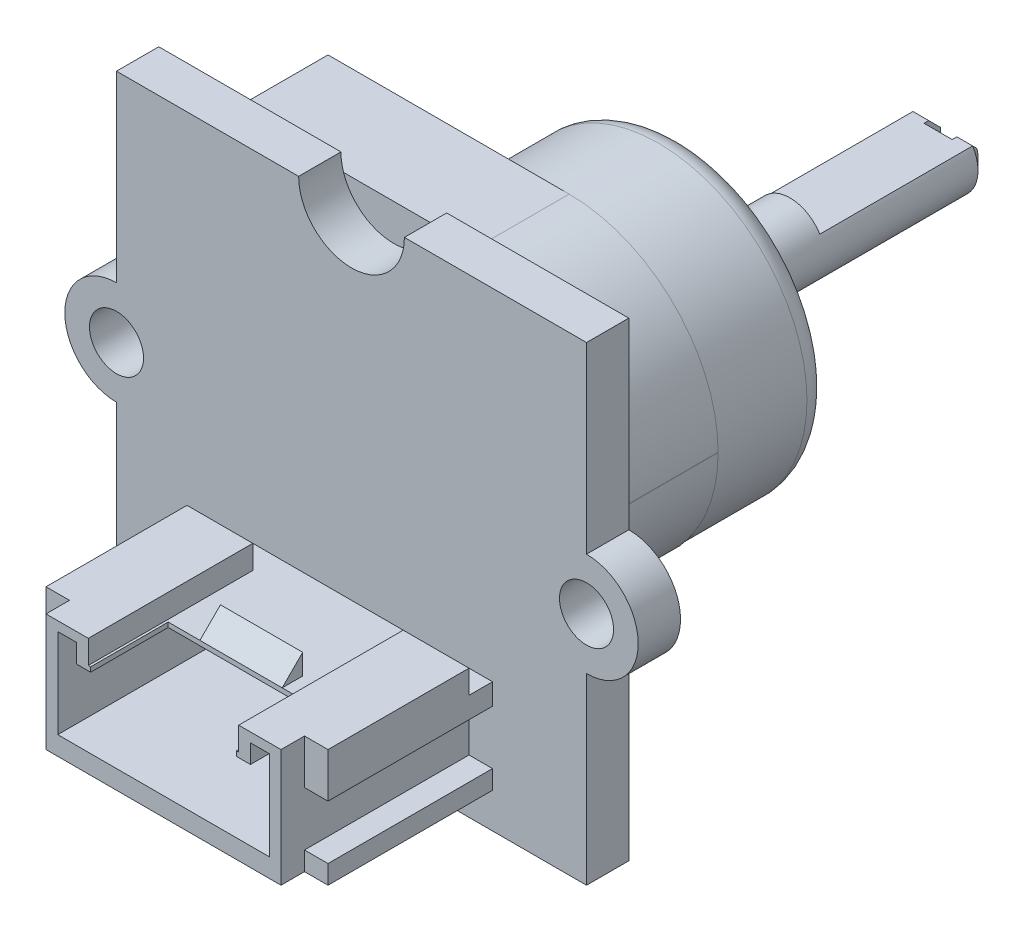
SolidWorks part; units mm, degrees
ref_plane "Plan de face" through (0, 0, 0) normal (0, 0, 1) x (1, 0, 0)
ref_plane "Plan de dessus" through (0, 0, 0) normal (0, 1, 0) x (1, 0, 0)
ref_plane "Plan de droite" through (0, 0, 0) normal (1, 0, 0) x (0, 0, -1)
sketch "Esquisse1" plane through (0, 0, 0) normal (0, 0, 1) x (1, 0, 0)
  line L0 (-2.7446, 10.9929) -> (-2.7446, -9.0071) construction
  line L1 (-12.7446, 10.9929) -> (-4.9946, 10.9929)
  line L2 (-12.7446, 10.9929) -> (-12.7446, 3.1929)
  line L3 (-12.7446, -9.0071) -> (-4.9946, -9.0071)
  line L4 (7.2554, 10.9929) -> (7.2554, 3.1929)
  line L5 (-12.7446, 0.9929) -> (7.2554, 0.9929) construction
  line L6 (-0.4946, 10.9929) -> (7.2554, 10.9929)
  line L7 (-0.4946, -9.0071) -> (7.2554, -9.0071)
  line L8 (-12.7446, -1.2071) -> (-12.7446, -9.0071)
  line L9 (7.2554, -1.2071) -> (7.2554, -9.0071)
  arc A0 (-4.9946, 10.9929) -> (-0.4946, 10.9929) centre (-2.7446, 10.9929) ccw
  arc A1 (-0.4946, -9.0071) -> (-4.9946, -9.0071) centre (-2.7446, -9.0071) ccw
  arc A2 (-12.7446, 3.1929) -> (-12.7446, -1.2071) centre (-12.7446, 0.9929) ccw
  arc A3 (7.2554, -1.2071) -> (7.2554, 3.1929) centre (7.2554, 0.9929) ccw
  circle A4 centre (-12.7446, 0.9929) radius 1.15
  circle A5 centre (7.2554, 0.9929) radius 1.15
  dimension "D1" = 20
  dimension "D2" = 20
extrude "Boss.-Extru.1" add sketch "Esquisse1" along normal blind 1.8
sketch "Esquisse2" plane through (0, 0, 1.8) normal (0, 0, 1) x (1, 0, 0)
  line L0 (-12.7446, -1.2071) -> (-12.7446, -9.0071) construction
  line L1 (-8.7446, -7.5071) -> (3.2554, -7.5071)
  line L2 (-8.7446, -7.5071) -> (-8.7446, -6.7071)
  line L3 (-8.7446, -2.5071) -> (3.2554, -2.5071)
  line L4 (3.2554, -7.5071) -> (3.2554, -6.7071)
  line L5 (-12.7446, -9.0071) -> (-4.9946, -9.0071) construction
  line L6 (3.2554, -4.4071) -> (2.2554, -4.4071)
  line L7 (-8.7446, -4.4071) -> (-7.7446, -4.4071)
  line L9 (-8.7446, -6.7071) -> (-7.7446, -6.7071)
  line L10 (-7.7446, -4.4071) -> (-7.7446, -6.7071)
  line L11 (2.2554, -4.4071) -> (2.2554, -6.7071)
  line L12 (2.2554, -6.7071) -> (3.2554, -6.7071)
  line L13 (-8.7446, -4.4071) -> (-8.7446, -2.5071)
  line L14 (3.2554, -4.4071) -> (3.2554, -2.5071)
  dimension "D1" = 12
  dimension "D2" = 5
  dimension "D3" = 4
  dimension "D4" = 1.5
  dimension "D5" = 1.9
  dimension "D6" = 1
  dimension "D7" = 2.3
extrude "Boss.-Extru.2" add sketch "Esquisse2" along normal blind 8
sketch "Esquisse3" plane through (0, 0, 9.8) normal (0, 0, 1) x (1, 0, 0)
  line L0 (-8.7446, -7.5071) -> (3.2554, -7.5071) construction
  line L1 (-6.4446, -3.7071) -> (0.9554, -3.7071)
  line L2 (-7.2446, -3.7071) -> (-7.2446, -6.7071)
  line L3 (-7.2446, -6.7071) -> (1.7554, -6.7071)
  line L4 (1.7554, -3.7071) -> (1.7554, -6.7071)
  line L5 (-7.7446, -4.4071) -> (-7.7446, -6.7071) construction
  line L6 (-7.2446, -3.7071) -> (-7.2446, -2.9071)
  line L7 (-7.2446, -2.9071) -> (-6.4446, -2.9071)
  line L8 (-6.4446, -2.9071) -> (-6.4446, -3.7071)
  line L9 (1.7554, -3.7071) -> (1.7554, -2.9071)
  line L10 (1.7554, -2.9071) -> (0.9554, -2.9071)
  line L11 (0.9554, -2.9071) -> (0.9554, -3.7071)
  dimension "D1" = 3
  dimension "D2" = 0.8
  dimension "D3" = 9
  dimension "D4" = 0.5
extrude "Enlèv. mat.-Extru.1" cut sketch "Esquisse3" against normal blind 7
sketch "Esquisse4" plane through (0, -2.5071, 0) normal (0, 1, 0) x (1, 0, 0)
  line L0 (-8.7446, -1.8) -> (3.2554, -1.8)
  line L1 (3.2554, -1.8) -> (3.2554, -2.8)
  line L2 (3.2554, -9.8) -> (3.2554, -1.8) construction
  line L3 (3.2554, -2.8) -> (0.4554, -2.8)
  line L4 (-8.7446, -1.8) -> (-8.7446, -2.8)
  line L5 (-8.7446, -9.8) -> (-8.7446, -1.8) construction
  line L6 (-8.7446, -2.8) -> (-5.9446, -2.8)
  line L7 (-5.9446, -2.8) -> (-5.9446, -9.8)
  line L8 (3.2554, -9.8) -> (-8.7446, -9.8) construction
  line L9 (0.4554, -2.8) -> (0.4554, -9.8)
  line L10 (0.4554, -9.8) -> (-5.9446, -9.8)
  line L11 (-2.7446, -9.8) -> (-2.7446, -3.7286) construction
  line L13 (-4.4946, -5.6264) -> (-0.9946, -5.6264)
  line L14 (-4.4946, -5.6264) -> (-4.4946, -6.5)
  line L15 (-4.4946, -6.5) -> (-0.9946, -6.5)
  line L16 (-0.9946, -5.6264) -> (-0.9946, -6.5)
  point P22 (-4.4946, -6.0632)
  dimension "D1" = 3.3
  dimension "D2" = 3.5
  dimension "D3" = 1.75
  dimension "D4" = 2.8
  dimension "D5" = 2.8
extrude "Enlèv. mat.-Extru.2" cut sketch "Esquisse4" against normal blind 1
sketch "Esquisse5" plane through (0, -2.5071, 0) normal (0, 1, 0) x (1, 0, 0)
  line L0 (-8.7446, -9.8) -> (-8.7446, -2.8) construction
  line L1 (-8.7446, -9.8) -> (-7.7446, -9.8)
  line L2 (-8.7446, -9.8) -> (-8.7446, -8.8)
  line L3 (-8.7446, -8.8) -> (-7.7446, -8.8)
  line L4 (-7.7446, -9.8) -> (-7.7446, -8.8)
  line L5 (-5.9446, -9.8) -> (-8.7446, -9.8) construction
  line L7 (3.2554, -9.8) -> (2.2554, -9.8)
  line L8 (3.2554, -9.8) -> (3.2554, -8.8)
  line L9 (3.2554, -8.8) -> (2.2554, -8.8)
  line L10 (2.2554, -9.8) -> (2.2554, -8.8)
  dimension "D1" = 1
  dimension "D2" = 1
  dimension "D3" = 1
extrude "Enlèv. mat.-Extru.3" cut sketch "Esquisse5" against normal blind 11
sketch "Esquisse6" plane through (0, -3.5071, 0) normal (0, 1, 0) x (1, 0, 0)
  line L0 (-5.9446, -9.8) -> (0.4554, -9.8) construction
  line L1 (-5.8446, -9.8) -> (0.3554, -9.8)
  line L2 (-5.8446, -9.8) -> (-5.8446, -6.5)
  line L3 (-5.8446, -6.5) -> (0.3554, -6.5)
  line L4 (0.3554, -9.8) -> (0.3554, -6.5)
  line L5 (-8.7446, -8.8) -> (-8.7446, -2.8) construction
  dimension "D1" = 6.2
  dimension "D2" = 2.9
  dimension "D3" = 3.3
extrude "Enlèv. mat.-Extru.4" cut sketch "Esquisse6" against normal blind 1
chamfer "Chanfrein1" distance 1 angle 45 1 edges at (-2.7446, -2.5071, 6.5)
sketch "Esquisse7" plane through (0, 0, 0) normal (0, 0, -1) x (-1, 0, 0)
  line L0 (12.7446, 10.9929) -> (12.7446, 3.1929) construction
  line L1 (9.5446, 10.2929) -> (-0.7154, 10.2929)
  line L2 (9.5446, 10.2929) -> (9.5446, -2.4071)
  line L3 (9.5446, -2.4071) -> (-0.7154, -2.4071)
  line L4 (-7.0554, 3.9529) -> (-7.0554, 3.9329)
  line L5 (0.4946, -9.0071) -> (-7.2554, -9.0071) construction
  arc A0 (-0.7154, -2.4071) -> (-7.0554, 3.9329) centre (-0.7154, 3.9329) cw
  arc A1 (-0.7154, 10.2929) -> (-7.0554, 3.9529) centre (-0.7154, 3.9529) ccw
  point P10 (-7.0554, -2.4071)
  dimension "D5" = 6.34
  dimension "D1" = 12.7
  dimension "D2" = 16.6
  dimension "D3" = 3.2
  dimension "D4" = 6.6
extrude "Boss.-Extru.3" add sketch "Esquisse7" along normal blind 4
sketch "Esquisse8" plane through (0, 0, -4) normal (0, 0, -1) x (-1, 0, 0)
  circle A0 centre (-0.7154, 3.9529) radius 6.32
extrude "Boss.-Extru.4" add sketch "Esquisse8" along normal blind 4.8
fillet "Congé1" radius 1 1 edges at (-5.6046, 3.9529, -8.8)
sketch "Esquisse10" plane through (0, 0, -8.8) normal (0, 0, -1) x (-1, 0, 0)
  circle A0 centre (-0.7154, 3.9529) radius 1.75
extrude "Boss.-Extru.5" add sketch "Esquisse10" along normal blind 1.6
fillet "Congé2" radius 1 1 edges at (-1.0346, 3.9529, -8.8)
sketch "Esquisse11" plane through (0, 0, -10.4) normal (0, 0, -1) x (-1, 0, 0)
  circle A0 centre (-0.7154, 3.9529) radius 1.5
extrude "Boss.-Extru.6" add sketch "Esquisse11" along normal blind 10
sketch "Esquisse12" plane through (0, 0, -20.4) normal (0, 0, -1) x (-1, 0, 0)
  line L0 (-8.242, 4.7529) -> (13.7736, 4.7529) construction
  line L2 (-1.9842, 4.7529) -> (0.9061, 4.7529)
  line L3 (-1.9842, 4.7529) -> (-1.9842, 5.8484)
  line L4 (-1.9842, 5.8484) -> (0.9061, 5.8484)
  line L5 (0.9061, 4.7529) -> (0.9061, 5.8484)
  circle A0 centre (-0.7154, 3.9529) radius 1.5 construction
  dimension "D1" = 0.8
extrude "Enlèv. mat.-Extru.7" cut sketch "Esquisse12" against normal blind 7
chamfer "Chanfrein2" distance 0.5 angle 45 2 edges at (0.7154, 2.4529, -20.4) (0.7154, 4.7529, -20.4)
sketch "Esquisse13" plane through (0, 0, -20.4) normal (0, 0, -1) x (-1, 0, 0)
  line L1 (-1.3154, 4.9291) -> (-0.1154, 4.9291)
  line L2 (-1.3154, 4.9291) -> (-1.3154, 2.1018)
  line L3 (-1.3154, 2.1018) -> (-0.1154, 2.1018)
  line L4 (-0.1154, 4.9291) -> (-0.1154, 2.1018)
  arc A0 (-1.6693, 4.2529) -> (0.2386, 4.2529) centre (-0.7154, 3.9529) ccw construction
  dimension "D1" = 1.2
  dimension "D2" = 0.6
extrude "Enlèv. mat.-Extru.8" cut sketch "Esquisse13" against normal blind 0.7
